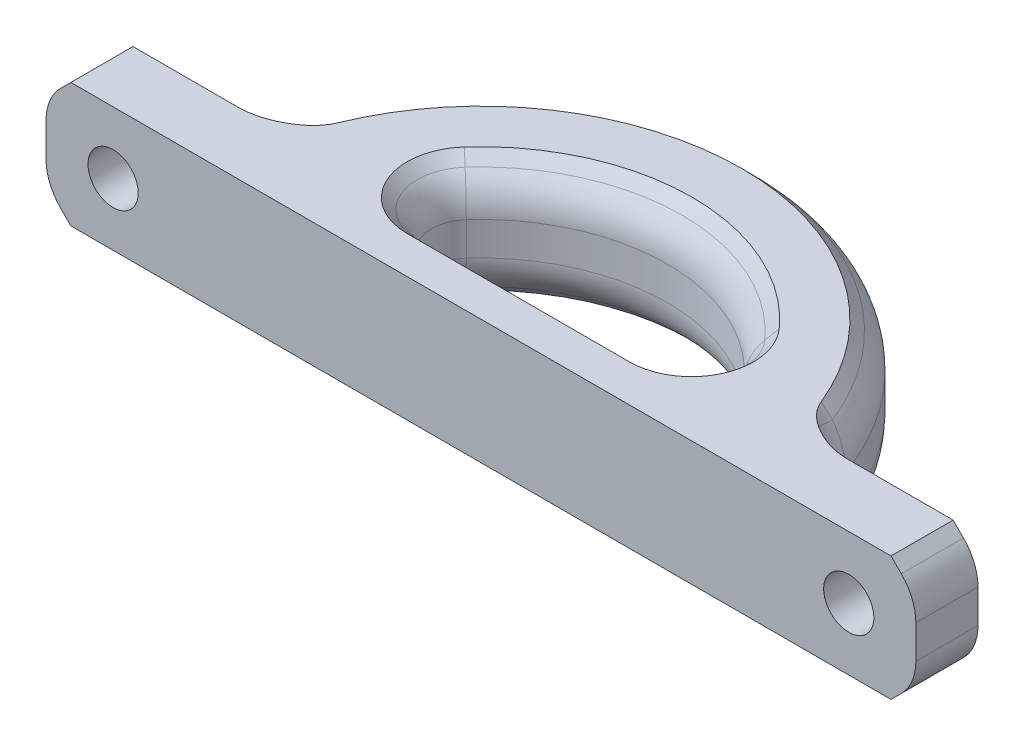
SolidWorks part; units mm, degrees
ref_plane "Front Plane" through (0, 0, 0) normal (0, 0, 1) x (1, 0, 0)
ref_plane "Top Plane" through (0, 0, 0) normal (0, 1, 0) x (1, 0, 0)
ref_plane "Right Plane" through (0, 0, 0) normal (1, 0, 0) x (0, 0, -1)
sketch "Sketch1" plane through (0, 0, 0) normal (0, 1, 0) x (1, 0, 0)
  line L0 (28.5114, 6.35) -> (44.45, 6.35)
  line L1 (-44.45, 0) -> (44.45, 0)
  line L2 (-44.45, 0) -> (-44.45, 6.35)
  line L3 (-44.45, 6.35) -> (-28.5114, 6.35)
  line L4 (44.45, 0) -> (44.45, 6.35)
  line L5 (-11.3592, 6.35) -> (11.3592, 6.35)
  arc A0 (28.5114, 6.35) -> (-28.5114, 6.35) centre (0, 0) ccw
  arc A1 (14.199, 12.7) -> (-14.199, 12.7) centre (0, 0) ccw
  arc A4 (14.199, 12.7) -> (11.3592, 6.35) centre (11.3592, 10.16) cw
  arc A5 (-14.199, 12.7) -> (-11.3592, 6.35) centre (-11.3592, 10.16) ccw
  point P3 (0, 0)
  point P9 (0, 19.05)
  point P10 (0, 0)
  point P11 (-24.1656, 16.6412)
  point P12 (0, 0)
  point P21 (-17.9605, 6.35)
  dimension "D2" = 10.16
  dimension "D5" = 3.81
  dimension "D1" = 12.7
  dimension "D3" = 88.9
  dimension "D4" = 6.35
extrude "Boss-Extrude1" add sketch "Sketch1" along normal blind 12.7
sketch "Sketch2" plane through (0, 0, -6.35) normal (0, 0, -1) x (-1, 0, 0)
  line L0 (0, 0) -> (0, 12.7) construction
  line L1 (28.5114, 12.7) -> (-28.5114, 12.7) construction
  line L2 (44.45, 12.7) -> (44.45, 0) construction
  circle A0 centre (37.592, 6.35) radius 2.5654
  circle A1 centre (-37.592, 6.35) radius 2.5654
  point P7 (0, 6.35)
  dimension "D1" = 5.1308
  dimension "D2" = 6.858
extrude "Cut-Extrude1" cut sketch "Sketch2" against normal through all
chamfer "Chamfer2" distance 2.54 angle 45 8 edges at (0, 0, -19.05) (-14.8373, 0, -8.6046) (14.8373, 0, -8.6046) (0, 0, -6.35) (0, 12.7, -6.35) (14.8373, 12.7, -8.6046) (-14.8373, 12.7, -8.6046) (0, 12.7, -19.05)
fillet "Fillet1" radius 5.08 8 edges at (-14.8373, 2.54, -8.6046) (0, 2.54, -6.35) (14.8373, 2.54, -8.6046) (14.8373, 10.16, -8.6046) (0, 10.16, -6.35) (-14.8373, 10.16, -8.6046) (0, 2.54, -19.05) (0, 10.16, -19.05)
chamfer "Chamfer3" distance 2.54 angle 45 2 edges at (0, 0, -29.21) (0, 12.7, -29.21) tangent propagation no
fillet "Fillet2" radius 5.08 2 edges at (0, 2.54, -29.21) (0, 10.16, -29.21)
fillet "Fillet3" radius 5.08 10 edges at (-27.9855, 10.2806, -6.35) (-28.2292, 2.9942, -6.35) (28.2292, 9.7058, -6.35) (27.9855, 2.4194, -6.35) (-28.5114, 6.35, -6.35) (28.5114, 6.35, -6.35)
chamfer "Chamfer4" distance 2.54 angle 45 4 edges at (44.45, 12.7, -3.175) (-44.45, 12.7, -3.175) (-44.45, 0, -3.175) (44.45, 0, -3.175)
fillet "Fillet4" radius 5.08 4 edges at (44.45, 10.16, -3.175) (44.45, 2.54, -3.175) (-44.45, 10.16, -3.175) (-44.45, 2.54, -3.175)
